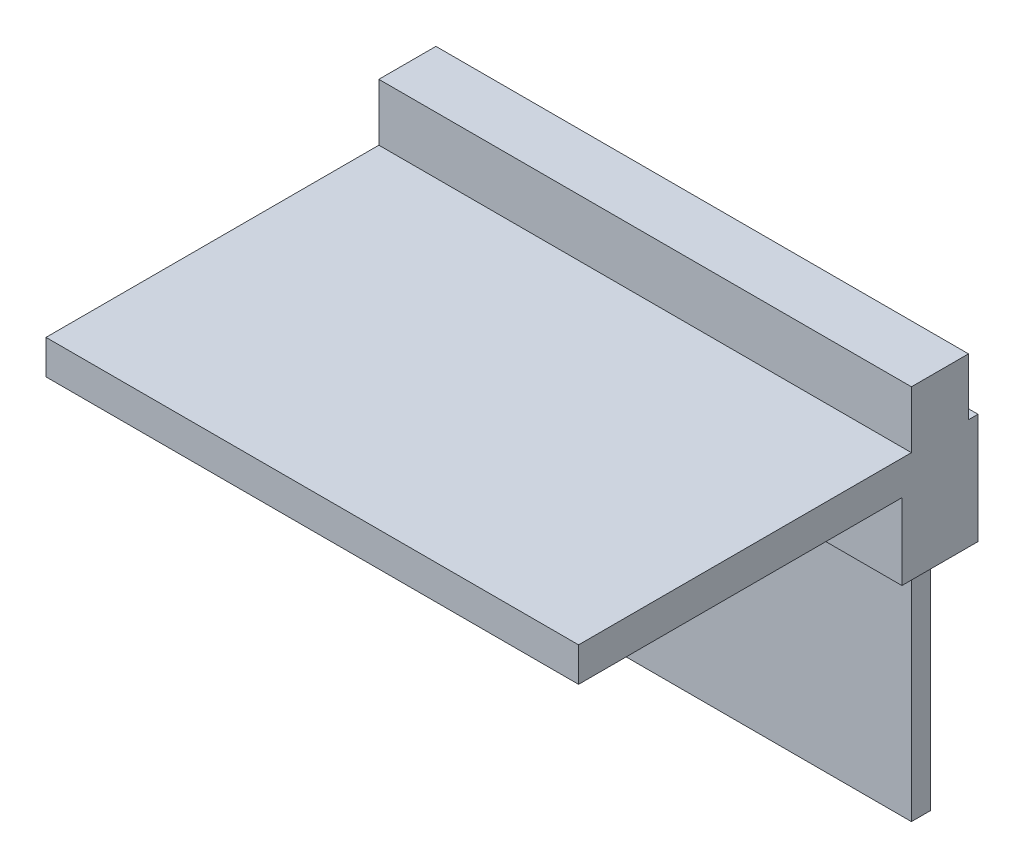
SolidWorks part; units mm, degrees
ref_plane "Спереди" through (0, 0, 0) normal (0, 0, 1) x (1, 0, 0)
ref_plane "Сверху" through (0, 0, 0) normal (0, 1, 0) x (1, 0, 0)
ref_plane "Справа" through (0, 0, 0) normal (1, 0, 0) x (0, 0, -1)
sketch "Эскиз1" plane through (0, 0, 0) normal (0, 1, 0) x (1, 0, 0)
  line L1 (-7, -5.25) -> (7, -5.25)
  line L2 (-7, -5.25) -> (-7, 5.25)
  line L3 (-7, 5.25) -> (7, 5.25)
  line L4 (7, -5.25) -> (7, 5.25)
  line L5 (-7, -5.25) -> (7, 5.25) construction
  line L6 (-7, 5.25) -> (7, -5.25) construction
  point P0 (0, 0)
  dimension "D1" = 14
  dimension "D2" = 10.5
extrude "Бобышка-Вытянуть1" add sketch "Эскиз1" along normal blind 0.9
sketch "Эскиз3" plane through (0, 0, 0) normal (0, -1, 0) x (1, 0, 0)
  line L0 (7, 5.25) -> (7, -5.25) construction
  line L1 (-7, -5.25) -> (7, -5.25)
  line L2 (-7, -5.25) -> (-7, -3.25)
  line L3 (-7, -3.25) -> (7, -3.25)
  line L4 (7, -5.25) -> (7, -3.25)
  dimension "D1" = 2
extrude "Бобышка-Вытянуть2" add sketch "Эскиз3" along normal blind 2
sketch "Эскиз4" plane through (0, -2, 0) normal (0, -1, 0) x (1, 0, 0)
  line L0 (0, 4.6207) -> (0, -6.1977) construction
  line L1 (6.5, -4.5) -> (-6.5, -4.5)
  line L2 (6.5, -4.5) -> (6.5, -4)
  line L3 (6.5, -4) -> (-6.5, -4)
  line L4 (-6.5, -4.5) -> (-6.5, -4)
  line L5 (6.5, -4.5) -> (-6.5, -4) construction
  line L6 (6.5, -4) -> (-6.5, -4.5) construction
  line L7 (7, -3.25) -> (-7, -3.25) construction
  point P0 (0, -4.25)
  dimension "D1" = 13
  dimension "D2" = 0.5
  dimension "D3" = 0.75
extrude "Бобышка-Вытянуть3" add sketch "Эскиз4" along normal blind 6
sketch "Эскиз8" plane through (0, 0.9, 0) normal (0, 1, 0) x (1, 0, 0)
  line L6 (7, 3.5) -> (-7, 3.5)
  line L7 (7, 3.5) -> (7, 5)
  line L8 (7, 5) -> (-7, 5)
  line L9 (-7, 3.5) -> (-7, 5)
  line L10 (7, 3.5) -> (-7, 5) construction
  line L11 (7, 5) -> (-7, 3.5) construction
  point P0 (0, 4.25)
  point P6 (0, 0)
  dimension "D1" = 1.5
  dimension "D2" = 14
extrude "Бобышка-Вытянуть4" add sketch "Эскиз8" along normal blind 1.5
